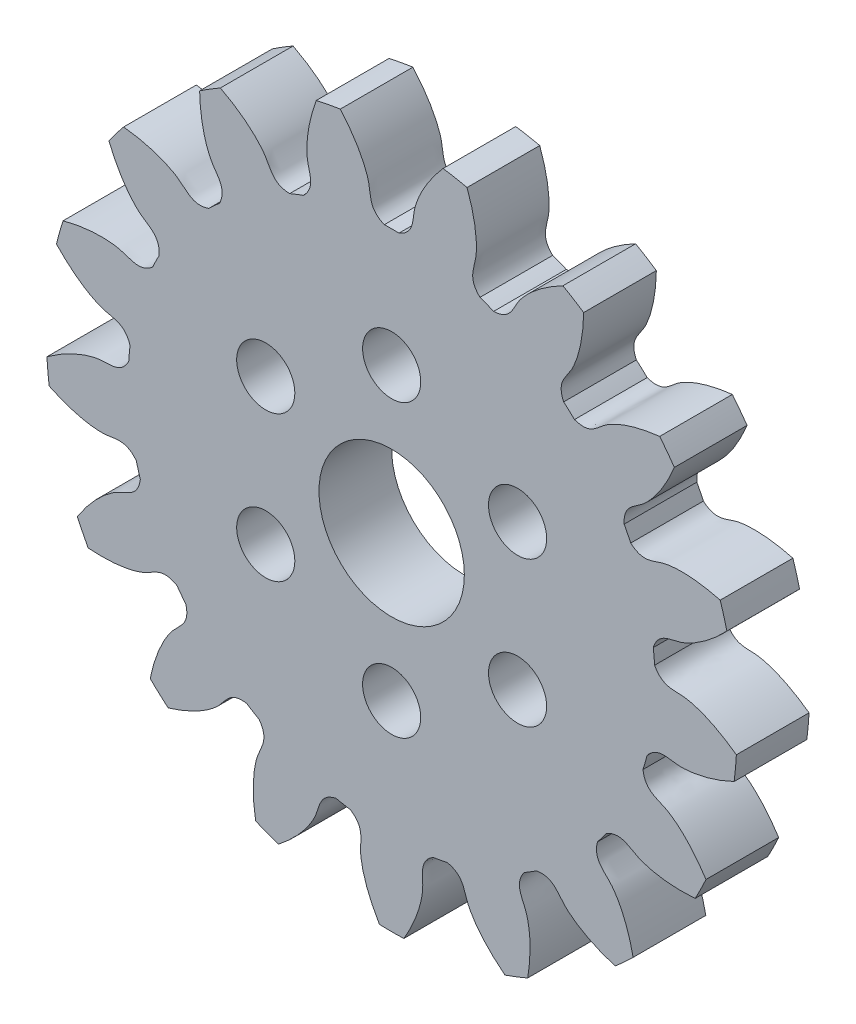
SolidWorks part; units mm, degrees
material "Thornel Mat VMA"
ref_plane "前视基准面" through (0, 0, 0) normal (0, 0, 1) x (1, 0, 0)
ref_plane "上视基准面" through (0, 0, 0) normal (0, 1, 0) x (1, 0, 0)
ref_plane "右视基准面" through (0, 0, 0) normal (1, 0, 0) x (0, 0, -1)
sketch "草图1" plane through (0, 0, 0) normal (0, 0, 1) x (1, 0, 0)
  circle A0 centre (0, 0) radius 19
extrude "凸台-拉伸1" add sketch "草图1" along normal blind 4
ref_axis "基准轴1" through (0, 0, 4) along (0, 0, -1)
sketch "草图2" plane through (0, 0, 0) normal (0, 0, 1) x (1, 0, 0)
  line L0 (0, 0) -> (0, 19) construction
  circle A0 centre (0, 0) radius 19 construction
  arc A1 (0.4034, 14.4944) -> (-0.4034, 14.4944) centre (0, 0) ccw
  arc A2 (6.2313, 21.4814) -> (-6.2313, 21.4814) centre (0, 0) ccw
  spline S0 degree 3 poles (0.4034, 14.4944) (1.2558, 14.8496) (1.1324, 15.5096) (1.2766, 16.1296) (1.29, 16.1823) (1.306, 16.2408) (1.3251, 16.3052) (1.3474, 16.3752) (1.3731, 16.4508) (1.4025, 16.5319) (1.4359, 16.6184) (1.4733, 16.7101) (1.5152, 16.8068) (1.5616, 16.9086) (1.6128, 17.0151) (1.669, 17.1264) (1.7304, 17.2421) (1.7972, 17.3621) (1.8696, 17.4863) (1.9478, 17.6145) (2.032, 17.7465) (2.1224, 17.8821) (2.2191, 18.0211) (2.3223, 18.1634) (2.4322, 18.3086) (2.5489, 18.4566) (2.6727, 18.6072) (2.8035, 18.7601) (2.9417, 18.9152) (3.0873, 19.0722) (3.2404, 19.2308) (3.4012, 19.3908) (3.5698, 19.552) (3.7462, 19.7141) (3.9307, 19.8769) (4.1233, 20.0401) (4.324, 20.2035) (4.533, 20.3667) (4.7503, 20.5295) (4.9761, 20.6917) (5.2103, 20.853) (5.453, 21.0131) (5.7916, 21.2269) (6.0532, 21.3811) (6.2313, 21.4814) knots 0 0 0 0 0.193883 0.199024 0.204851 0.211363 0.21856 0.226443 0.235011 0.244265 0.254205 0.264829 0.27614 0.288136 0.300817 0.314184 0.328236 0.342973 0.358397 0.374505 0.391299 0.408779 0.426944 0.445795 0.465331 0.485552 0.506459 0.528051 0.550329 0.573293 0.596941 0.621276 0.646296 0.672001 0.698392 0.725468 0.753229 0.781677 0.810809 0.840627 0.871131 0.90232 0.934195 1 1 1 1
  spline S1 degree 3 poles (-0.4034, 14.4944) (-1.2558, 14.8496) (-1.1324, 15.5096) (-1.2766, 16.1296) (-1.29, 16.1823) (-1.306, 16.2408) (-1.3251, 16.3052) (-1.3474, 16.3752) (-1.3731, 16.4508) (-1.4025, 16.5319) (-1.4359, 16.6184) (-1.4733, 16.7101) (-1.5152, 16.8068) (-1.5616, 16.9086) (-1.6128, 17.0151) (-1.669, 17.1264) (-1.7304, 17.2421) (-1.7972, 17.3621) (-1.8696, 17.4863) (-1.9478, 17.6145) (-2.032, 17.7465) (-2.1224, 17.8821) (-2.2191, 18.0211) (-2.3223, 18.1634) (-2.4322, 18.3086) (-2.5489, 18.4566) (-2.6727, 18.6072) (-2.8035, 18.7601) (-2.9417, 18.9152) (-3.0873, 19.0722) (-3.2404, 19.2308) (-3.4012, 19.3908) (-3.5698, 19.552) (-3.7462, 19.7141) (-3.9307, 19.8769) (-4.1233, 20.0401) (-4.324, 20.2035) (-4.533, 20.3667) (-4.7503, 20.5295) (-4.9761, 20.6917) (-5.2103, 20.853) (-5.453, 21.0131) (-5.7916, 21.2269) (-6.0532, 21.3811) (-6.2313, 21.4814) knots 0 0 0 0 0.193883 0.199024 0.204851 0.211363 0.21856 0.226443 0.235011 0.244265 0.254205 0.264829 0.27614 0.288136 0.300817 0.314184 0.328236 0.342973 0.358397 0.374505 0.391299 0.408779 0.426944 0.445795 0.465331 0.485552 0.506459 0.528051 0.550329 0.573293 0.596941 0.621276 0.646296 0.672001 0.698392 0.725468 0.753229 0.781677 0.810809 0.840627 0.871131 0.90232 0.934195 1 1 1 1
extrude "切除-拉伸1" cut sketch "草图2" along normal through all
pattern_circular "阵列(圆周)1" count 17 every 21.176 about axis through (0, 0, 4) along (0, 0, -1) of "切除-拉伸1"
sketch "草图3" plane through (0, 0, 0) normal (0, 0, 1) x (1, 0, 0)
  circle A0 centre (0, 0) radius 17 construction
  dimension "Dn" = 34
sketch "草图4" plane through (0, 0, 4) normal (0, 0, 1) x (1, 0, 0)
  circle A0 centre (0, 0) radius 4
  circle A1 centre (0, 0) radius 8 construction
  circle A2 centre (0, 8) radius 1.6
  circle A3 centre (6.9282, 4) radius 1.6
  circle A4 centre (6.9282, -4) radius 1.6
  circle A5 centre (0, -8) radius 1.6
  circle A6 centre (-6.9282, -4) radius 1.6
  circle A7 centre (-6.9282, 4) radius 1.6
  point P15 (0, 0)
  dimension "D1" = 3.2
  dimension "D2" = 16
  dimension "D3" = 8
  dimension "D4" = 6
extrude "切除-拉伸2" cut sketch "草图4" against normal blind 10
